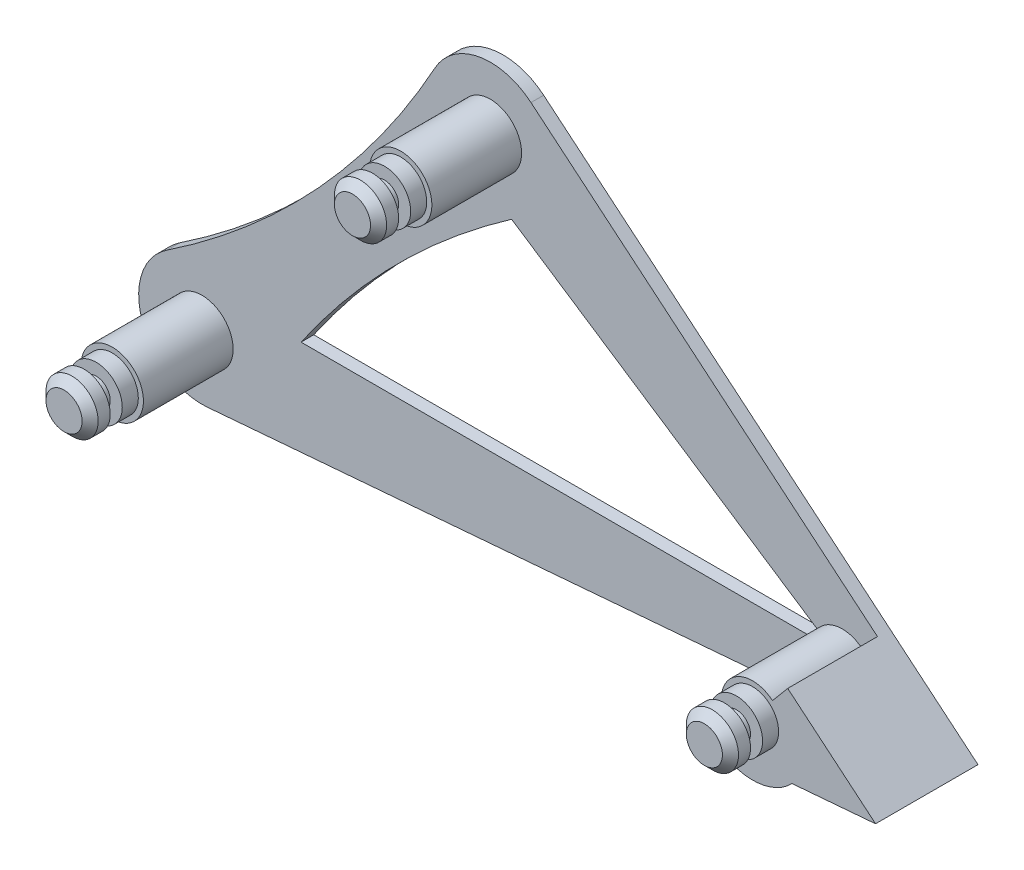
SolidWorks part; units mm, degrees
ref_plane "Plan de face" through (0, 0, 0) normal (1, 0, 0) x (0, 1, 0)
ref_plane "Plan de dessus" through (0, 0, 0) normal (0, 0, 1) x (0, 1, 0)
ref_plane "Plan de droite" through (0, 0, 0) normal (0, 1, 0) x (-1, 0, 0)
sketch "Esquisse1" plane through (0, 0, 0) normal (0, 0, 1) x (0, 1, 0)
  line L0 (0, 0) -> (0, 87.204) construction
  line L1 (0, 95.09) -> (39.1116, 59.1602) construction
  line L2 (39.1116, 59.1602) -> (36.9685, 55.9185)
  line L3 (19.5558, 77.1251) -> (0, 0) construction
  line L4 (-7.8588, 94.436) -> (0, 0)
  line L5 (31.5776, 56.8306) -> (6.2014, 18.4466)
  line L6 (5, 19.0487) -> (5, 88.9917)
  line L8 (34.9407, 61.9176) -> (5, 16.6293) construction
  line L9 (45.1656, 54.1066) -> (0, 0)
  line L10 (5, 16.6293) -> (5, 95.09) construction
  line L11 (0, 0) -> (0, 95.09) construction
  line L12 (34.7626, 52.5818) -> (0, 0) construction
  line L13 (39.1116, 59.1602) -> (0, 0) construction
  circle A0 centre (0, 95.09) radius 3.886
  circle A1 centre (39.1116, 59.1602) radius 3.886
  circle A2 centre (3.886, 15.3258) radius 3.886
  circle A3 centre (39.1116, 59.1602) radius 7.886
  circle A4 centre (0, 95.09) radius 7.886
  arc A5 (42.9159, 66.0679) -> (6.5609, 99.4653) centre (93.0858, 157.1666) cw
  arc A6 (32.5507, 54.7849) -> (-3.8042, 88.1823) centre (-53.9742, -2.9165) ccw
  dimension "D4" = 7.772
  dimension "D7" = 104
  dimension "D1" = 95.09
  dimension "D2" = 70.92
  dimension "D3" = 53.11
  dimension "D5" = 4
  dimension "D6" = 5
extrude "Boss.-Extru.1" add sketch "Esquisse1" along normal blind 1.58 contours A3 L5 A2 L6 L4 L9 | A2 | A3 A1 | A3 L5 | L5 A3 A5 A4 L6 | L6 A4 | A4 A0 | A0 | A1 region at (-90.741, -6.7078, 0) region at (-102.3255, -2.5236, 0) region at (-76.7286, 20.3155, 0) region at (-86.0762, 2.7591, 0) region at (-51.5083, 38.7002, 0) region at (-56.189, 31.722, 0) region at (-15.3258, 3.886, 0) region at (-95.09, 0, 0) region at (-55.8343, 40.8998, 0)
extrude "Boss.-Extru.2" add sketch "Esquisse1<3>" along normal blind 11.18 from surface contours A2 | A1 | A0 starting at face at (-44.4997, 12.195, 1.58)
sketch "Esquisse1<3>" plane through (0, 0, 0) normal (0, 0, 1) x (0, 1, 0) same geometry as "Esquisse1"
sketch "Esquisse2" plane through (0, 0, 12.76) normal (0, 0, 1) x (1, 0, 0)
  circle A0 centre (-95.09, 0) radius 3.25
  circle A1 centre (-59.1602, 39.1116) radius 3.25
  circle A2 centre (-15.3258, 3.886) radius 3.25
  dimension "D1" = 6.5
extrude "Boss.-Extru.3" add sketch "Esquisse2" along normal blind 6
sketch "Esquisse3" plane through (0, 0, 18.76) normal (0, 0, 1) x (1, 0, 0)
  circle A1 centre (-59.1602, 39.1116) radius 1.75
  circle A2 centre (-95.09, 0) radius 1.75
  circle A3 centre (-95.09, 0) radius 1.75
  circle A4 centre (-15.3258, 3.886) radius 1.75
  circle A6 centre (-95.09, 0) radius 3.25
  circle A7 centre (-95.09, 0) radius 3.25
  circle A8 centre (-59.1602, 39.1116) radius 3.25
  circle A9 centre (-59.1602, 39.1116) radius 3.25
  circle A10 centre (-15.3258, 3.886) radius 3.25
  circle A11 centre (-15.3258, 3.886) radius 3.25
  dimension "D1" = 1.5
  dimension "D2" = 0
  dimension "D3" = 0
  dimension "D4" = 0
extrude "Enlèv. mat.-Extru.1" cut sketch "Esquisse3" against normal blind 1.5 from offset 2.5 offset against normal yes
chamfer "Chanfrein1" distance 1 angle 45 3 edges at (-12.0758, 3.886, 18.76) (-55.9102, 39.1116, 18.76) (-91.84, 0, 18.76)
sketch "Esquisse4" plane through (0, 0, 1.58) normal (0, 0, 1) x (1, 0, 0)
  line L0 (-94.436, -7.8588) -> (0, 0) construction
  line L1 (-54.1066, 45.1656) -> (0, 0) construction
  line L2 (-10.4091, -0.8662) -> (0, 0)
  line L3 (-54.1066, 45.1656) -> (0, 0)
  line L4 (-15.3258, 3.886) -> (-10.9438, 9.1354)
  line L5 (-15.3258, 3.886) -> (-19.3893, -1.6136)
  circle A1 centre (-15.3258, 3.886) radius 6.8379
  arc A2 (-19.0487, 5) -> (-18.4466, 6.2014) centre (-15.3258, 3.886) ccw construction
  line M7 (-94.436, -7.8588) -> (0, 0)
  line M8 (0, 0) -> (-54.1066, 45.1656)
  arc M11 (-18.4466, 6.2014) -> (-19.0487, 5) centre (-15.3258, 3.886) cw
extrude "Boss.-Extru.4" add sketch "Esquisse4" along normal blind 11.18 contours A1 M7 M8 | A1 M7 | A1 L4 L5 M7 M11 region at (-6.0309, 2.1771, 1.58) region at (-14.9119, -1.0873, 1.58) region at (-14.8424, -1.923, 1.58)
